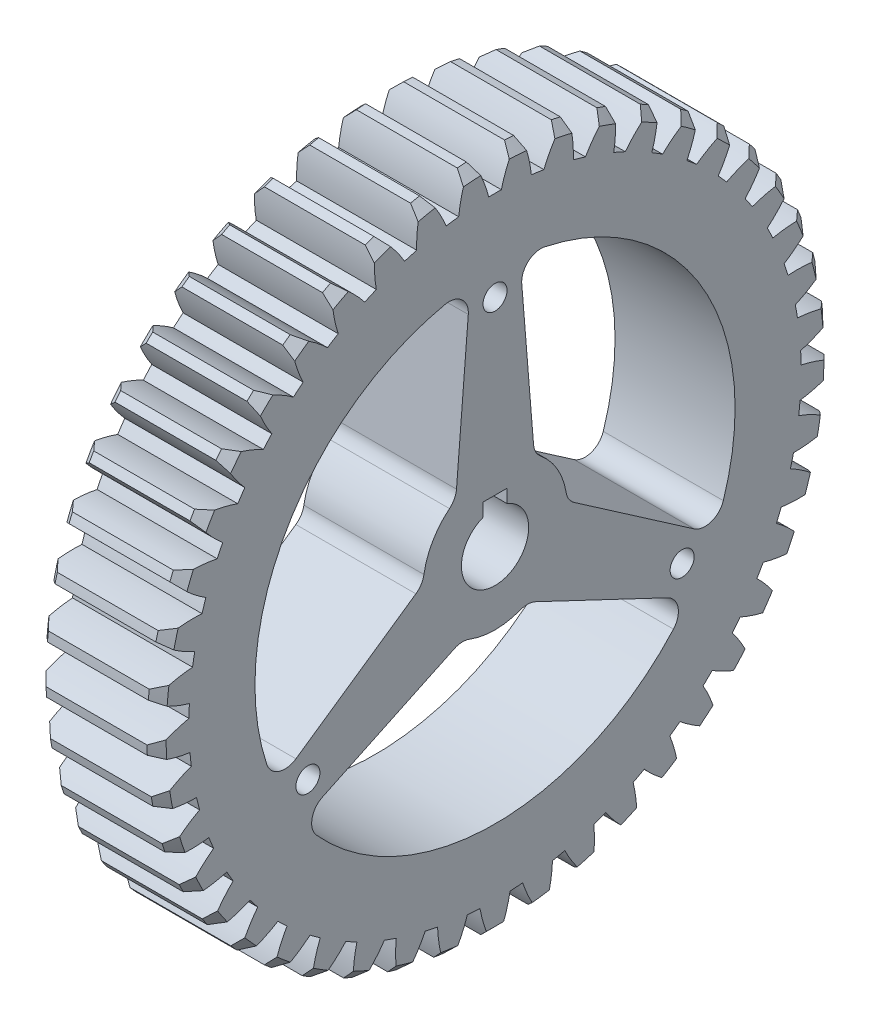
SolidWorks part; units mm, degrees
ref_plane "Plane1" through (0, 0, 0) normal (0, 0, 1) x (1, 0, 0)
ref_plane "Plane2" through (0, 0, 0) normal (0, 1, 0) x (1, 0, 0)
ref_plane "Plane3" through (0, 0, 0) normal (1, 0, 0) x (0, 0, -1)
sketch "HoldingSke" plane through (0, 0, 0) normal (0, 1, 0) x (1, 0, 0)
  line L0 (0, 0) -> (0.2357, -0.2357)
  line L1 (-15, 0) -> (100, 0) construction
  line L2 (0, 0) -> (-2.1039, 2.3779)
  line L3 (0, 0) -> (-11.863, 4.5341)
  line L4 (0, 0) -> (6.1066, 6.1066)
  line L5 (0, 0) -> (-46.8476, -17.4728)
  line L6 (0, 0) -> (-24.8689, -16.7791)
  line L7 (-2.1039, 2.3779) -> (8.6586, 51.2059)
  line L8 (-76.2, 54.61) -> (-73.9, 54.61)
  line L9 (-71.009, 38.7566) -> (-53.1078, 45.2721)
  line L10 (-76.2, 71.12) -> (104.1128, 71.12)
  line L11 (0, 0) -> (-30, 0)
  line L12 (-76.2, 101.6) -> (-76.093, 101.6)
  line L13 (24.9733, 27.94) -> (52.9518, 28.4284)
  line L14 (24.9733, 27.94) -> (24.9743, 27.94)
  line L15 (24.9733, 27.94) -> (100.4006, 29.5858)
  line L16 (-63.627, -3) -> (-12.827, -3)
  circle A0 centre (0, 0) radius 7
  circle A1 centre (0, 0) radius 37.5
  circle A2 centre (0, 0) radius 37.5
  circle A3 centre (0, 0) radius 7
  dimension "Num_teeth" = 45
  dimension "Pitch_radius" = 180.3128
  dimension "Width" = 30
sketch "BasProSke" plane through (0, 0, 0) normal (0, 1, 0) x (1, 0, 0)
  line L0 (-10, 0) -> (60, 0) construction
  line L1 (0, 0) -> (0, 70.5)
  line L2 (0, 0) -> (25, 0)
  line L3 (25, 0) -> (25, 70.5)
  line L4 (25, 70.5) -> (0, 70.5)
  dimension "Thickness" = 25
  dimension "Diameter" = 141
revolve "Base-Revolve" add sketch "BasProSke" angle 360 about L0
chamfer "倒角1" distance 2 angle 45 2 edges at (25, 0, 70.5) (0, 0, 70.5)
sketch "TooCutSke" plane through (0, 0, 0) normal (1, 0, 0) x (0, 0, -1)
  line L1 (0, 0) -> (0, 107) construction
  line L2 (0, 0) -> (-2.5429, 67.4521) construction
  line L3 (0, 0) -> (-9.4123, 134.6016) construction
  line L4 (-2.5429, 67.4521) -> (-4.7061, 67.3008) construction
  arc A0 (1.3167, 63.7354) -> (-1.3167, 63.7354) centre (0, 0) ccw
  arc A1 (3.9813, 70.4129) -> (-3.9813, 70.4129) centre (0, 0) ccw
  circle A2 centre (0, 0) radius 67.5 construction
  circle A3 centre (0, 0) radius 63.4293 construction
  arc A4 (-1.3167, 63.7354) -> (-3.9813, 70.4129) centre (-27.5029, 57.1564) ccw
  arc A5 (3.9813, 70.4129) -> (1.3167, 63.7354) centre (27.5029, 57.1564) ccw
extrude "ToothCut" cut sketch "TooCutSke" along normal through all
fillet "Breaks" [suppressed] radius 0.06 tangent propagation no
fillet "RootFillets" [suppressed] radius 0.751
pattern_circular "TeethCuts" count 45 every 8 about axis through (-10, 0, 0) along (1, 0, 0) of "ToothCut", "RootFillets", "Breaks"
sketch "HubNeaOneSke" plane through (0, 0, 0) normal (-1, 0, 0) x (0, 0, 1)
  circle A0 centre (0, 0) radius 37.5
  dimension "Diameter" = 75
extrude "HubNearOne" [suppressed] add sketch "HubNeaOneSke" along normal blind 25.0001
sketch "HubNeaBotSke" plane through (0, 0, 0) normal (-1, 0, 0) x (0, 0, 1)
  circle A0 centre (0, 0) radius 37.5
  dimension "Diameter" = 75
extrude "HubNearBoth" [suppressed] add sketch "HubNeaBotSke" along normal blind 12.5
ref_plane "FarPln" through (25, 0, 0) normal (1, 0, 0) x (0, 0, -1)
sketch "HubFarSke" plane through (25, 0, 0) normal (1, 0, 0) x (0, 0, -1)
  circle A0 centre (0, 0) radius 37.5
  dimension "Diameter" = 75
extrude "HubFar" [suppressed] add sketch "HubFarSke" along normal blind 12.5
sketch "BorSke" plane through (0, 0, 0) normal (1, 0, 0) x (0, 0, -1)
  circle A0 centre (0, 0) radius 7
  dimension "Diameter" = 14
extrude "Bore" cut sketch "BorSke" along normal mid plane 100.0001
sketch "KeySke" plane through (0, 0, 0) normal (1, 0, 0) x (0, 0, -1)
  line L0 (-2.5, 0) -> (-2.5, 9.3)
  line L1 (-2.5, 9.3) -> (2.5, 9.3)
  line L2 (2.5, 9.3) -> (2.5, 0)
  line L3 (0, 0) -> (0, 34) construction
  line L4 (-2.5, 0) -> (2.5, 0)
  dimension "Width" = 5
extrude "Keyway" cut sketch "KeySke" along normal mid plane 100.0001
pattern_circular "Keyway2" [suppressed] count 2 every 90 about axis through (-10, 0, 0) along (1, 0, 0) reverse direction yes
sketch "草图1" plane through (0, 0, 0) normal (1, 0, 0) x (0, 0, -1)
  line L2 (0, 0) -> (-12.9904, 7.5) construction
  line L3 (-5.1571, 49.7333) -> (-8.1725, 12.5782)
  line L4 (0, 67.7355) -> (0, 0) construction
  line L5 (-45.6489, -20.4005) -> (-14.9793, 0.7885)
  line L6 (45.6489, -20.4005) -> (14.9793, 0.7885)
  line L7 (5.1571, 49.7333) -> (8.1725, 12.5782)
  line L8 (-40.4918, -29.3328) -> (-6.8068, -13.3667)
  line L9 (40.4918, -29.3328) -> (6.8068, -13.3667)
  arc A0 (-8.1725, 12.5782) -> (-14.9793, 0.7885) centre (0, 0) ccw
  arc A1 (-5.1571, 49.7333) -> (-45.6489, -20.4005) centre (0, 0) ccw
  circle A3 centre (-12.9904, 7.5) radius 7 construction
  circle A4 centre (-0.5157, 54.9733) radius 7 construction
  arc A5 (45.6489, -20.4005) -> (5.1571, 49.7333) centre (0, 0) ccw
  arc A6 (14.9793, 0.7885) -> (8.1725, 12.5782) centre (0, 0) ccw
  arc A7 (-40.4918, -29.3328) -> (40.4918, -29.3328) centre (0, 0) ccw
  arc A8 (-6.8068, -13.3667) -> (6.8068, -13.3667) centre (0, 0) ccw
  dimension "D2" = 14
  dimension "D3" = 100
  dimension "D4" = 3
  dimension "D5" = 30
  dimension "D6" = 14
  dimension "D1" = 60
extrude "切除-拉伸1" cut sketch "草图1" along normal through all
sketch "草图2" plane through (0, 0, 0) normal (1, 0, 0) x (0, 0, -1)
  circle A0 centre (0, 45) radius 2.5
  circle A4 centre (0, 0) radius 45 construction
  circle A5 centre (38.9711, -22.5) radius 2.5
  circle A6 centre (-38.9711, -22.5) radius 2.5
  dimension "D1" = 5
  dimension "D2" = 90
  dimension "D3" = 3
extrude "切除-拉伸2" cut sketch "草图2" along normal through all
sketch "草图3" plane through (0, 0, 0) normal (1, 0, 0) x (0, 0, -1)
  circle A0 centre (0, 30) radius 2
  circle A1 centre (25.9808, -15) radius 2
  circle A2 centre (-25.9808, -15) radius 2
  dimension "D1" = 4
  dimension "D3" = 3
extrude "切除-拉伸3" cut sketch "草图3" along normal blind 10
fillet "圆角1" radius 4 12 edges at (12.5, 12.5782, -8.1725) (12.5, 0.7885, -14.9793) (12.5, -13.3667, -6.8068) (12.5, -13.3667, 6.8068) (12.5, 0.7885, 14.9793) (12.5, 12.5782, 8.1725) (12.5, 49.7333, 5.1571) (12.5, 49.7333, -5.1571) (12.5, -20.4005, -45.6489) (12.5, -29.3328, -40.4918) (12.5, -29.3328, 40.4918) (12.5, -20.4005, 45.6489)
equation "' \"Module@HoldingSke\" = 6.35"
equation "' \"Num_teeth@HoldingSke\" = 12"
equation "' \"Ap@HoldingSke\" =  20"
equation "' \"Ap@HoldingSke\" = 20"
equation "' \"Width@HoldingSke\" = 0.5 * 25.4"
equation "' \"Hub_dia@HoldingSke\"= 1 * 25.4"
equation "' \"Hub_dia@HoldingSke\" = 1 * 25.4"
equation "' \"Overall_len@HoldingSke\" = 1.0 * 25.4"
equation "' \"Bore@HoldingSke\" = 0.75 * 25.4"
equation "' \"T_dim@HoldingSke\" = 0.1 * 25.4"
equation "' \"Width@KeySke\" = 0.25 * 25.4"
equation "' \"Show_teeth@HoldingSke\" = 13"
equation "' \"Backlash@HoldingSke\" = 0.009 * 25.4"
equation "' \"Addendum_fac@HoldingSke\" = 1.0"
equation "' \"Dedendum_fac@HoldingSke\" = 1.25"
equation "' \"Dedendum_add@HoldingSke\" = 0.00005 * 25.4"
equation "' \"Clearance_fac@HoldingSke\" = 0.25"
equation "\"Pitch@HoldingSke\" = 1 / \"Module@HoldingSke\""
equation "\"Overcut_dia@TooCutSke\" = (\"Num_teeth@HoldingSke\" + 2 * \"Addendum_fac@HoldingSke\") / \"Pitch@HoldingSke\" + 0.002 * 25.4"
equation "\"Pitch_dia@TooCutSke\" = \"Num_teeth@HoldingSke\" / \"Pitch@HoldingSke\""
equation "\"Base_dia@TooCutSke\" = \"Num_teeth@HoldingSke\" / \"Pitch@HoldingSke\" * cos((\"Ap@HoldingSke\"  * 3.14159265 / 180))"
equation "\"Root_dia@TooCutSke\" = (\"Num_teeth@HoldingSke\" + 2) / \"Pitch@HoldingSke\" - 2 * (\"Addendum_fac@HoldingSke\" + \"Dedendum_fac@HoldingSke\") / \"Pitch@HoldingSke\" - \"Dedendum_add@HoldingSke\" * 2"
equation "\"Half_ang@TooCutSke\" = 180 / \"Num_teeth@HoldingSke\""
equation "\"Half_CT@TooCutSke\" = \"Num_teeth@HoldingSke\" / \"Pitch@HoldingSke\" * sin((3.14159265 / 2 / \"Num_teeth@HoldingSke\")) / 2 - 7 * \"Backlash@HoldingSke\" / 4"
equation "\"Flank_rad@TooCutSke\" = \"Num_teeth@HoldingSke\" / \"Pitch@HoldingSke\" / 5"
equation "\"Radius@RootFillets\" = \"Clearance_fac@HoldingSke\" / \"Pitch@HoldingSke\" + \"Dedendum_add@HoldingSke\""
equation "\"Break_rad@Breaks\" = 0.02 / \"Pitch@HoldingSke\""
equation "\"Thickness@HoldingSke\" = \"Width@HoldingSke\""
equation "\"OAL@HoldingSke\" = \"Thickness@HoldingSke\""
equation "\"MHD@HoldingSke\" = (\"Num_teeth@HoldingSke\" + 2) / \"Pitch@HoldingSke\" - 2 * (\"Addendum_fac@HoldingSke\" + \"Dedendum_fac@HoldingSke\")  / \"Pitch@HoldingSke\" - \"Dedendum_add@HoldingSke\" * 2"
equation "\"MBD@HoldingSke\" = (\"Num_teeth@HoldingSke\" + 2) / \"Pitch@HoldingSke\" - 2 * (\"Addendum_fac@HoldingSke\" + \"Dedendum_fac@HoldingSke\")  / \"Pitch@HoldingSke\" - \"Dedendum_add@HoldingSke\" * 2 - 0.002 * 25.4"
equation "\"MHD@HoldingSke\" = ((sgn( \"MHD@HoldingSke\" - \"Hub_dia@HoldingSke\" )-1)*( \"MHD@HoldingSke\" - \"Hub_dia@HoldingSke\" ))/-2+ \"Hub_dia@HoldingSke\""
equation "\"MBD@HoldingSke\" = ((sgn( \"MBD@HoldingSke\" - \"Bore@HoldingSke\" )-1)*( \"MBD@HoldingSke\" - \"Bore@HoldingSke\" ))/-2+ \"Bore@HoldingSke\""
equation "\"OAL@HoldingSke\" = ((sgn( \"OAL@HoldingSke\" - \"Overall_len@HoldingSke\" )+1)*( \"OAL@HoldingSke\" - \"Overall_len@HoldingSke\" ))/2 + \"Overall_len@HoldingSke\" + 0.000002 * 25.4"
equation "\"Num_teeth@TeethCuts\" = int( \"Show_teeth@HoldingSke\" ) + 1"
equation "\"Num_teeth@TeethCuts\" = ((sgn( \"Num_teeth@TeethCuts\" - \"Num_teeth@HoldingSke\" )-1)*( \"Num_teeth@TeethCuts\" - \"Num_teeth@HoldingSke\" ))/-2+ \"Num_teeth@HoldingSke\""
equation "\"Num_teeth@TeethCuts\" = ((sgn( \"Num_teeth@TeethCuts\" - 2.0)+1)*( \"Num_teeth@TeethCuts\" - 2.0))/2 +2.0"
equation "\"Angle@TeethCuts\" = 360.0 / \"Num_teeth@HoldingSke\""
equation "\"Diameter@BasProSke\" = (\"Num_teeth@HoldingSke\" + 2 * \"Addendum_fac@HoldingSke\") / \"Pitch@HoldingSke\""
equation "' \"Fillet_rad@BasProSke\" =  \"Thickness@HoldingSke\" * 0.05"
equation "' \"Fillet_rad@BasProSke\" = \"Thickness@HoldingSke\" * 0.05"
equation "\"MHD@HoldingSke\" = ((sgn( \"MHD@HoldingSke\" - \"Root_dia@TooCutSke\" )-1)*( \"MHD@HoldingSke\" - \"Root_dia@TooCutSke\" ))/-2+ \"Root_dia@TooCutSke\""
equation "\"Diameter@HubNeaOneSke\" = \"MHD@HoldingSke\""
equation "\"Length@HubNearOne\" = \"OAL@HoldingSke\" - \"Thickness@BasProSke\""
equation "\"Diameter@HubNeaBotSke\" = \"MHD@HoldingSke\""
equation "\"Length@HubNearBoth\" = ( \"OAL@HoldingSke\" - \"Thickness@BasProSke\" ) / 2.0"
equation "\"Thickness@FarPln\" = \"Thickness@BasProSke\""
equation "\"Diameter@HubFarSke\" = \"MHD@HoldingSke\""
equation "\"Length@HubFar\" = ( \"OAL@HoldingSke\" - \"Thickness@BasProSke\" ) / 2.0"
equation "\"Diameter@BorSke\" = \"MBD@HoldingSke\""
equation "\"D1@Bore\" = \"OAL@HoldingSke\" * 2.0"
equation "\"D1@Keyway\" = \"OAL@HoldingSke\" * 2.0"
equation "\"Offset@KeySke\" = \"T_dim@HoldingSke\" + \"MBD@HoldingSke\" / 2.0"
